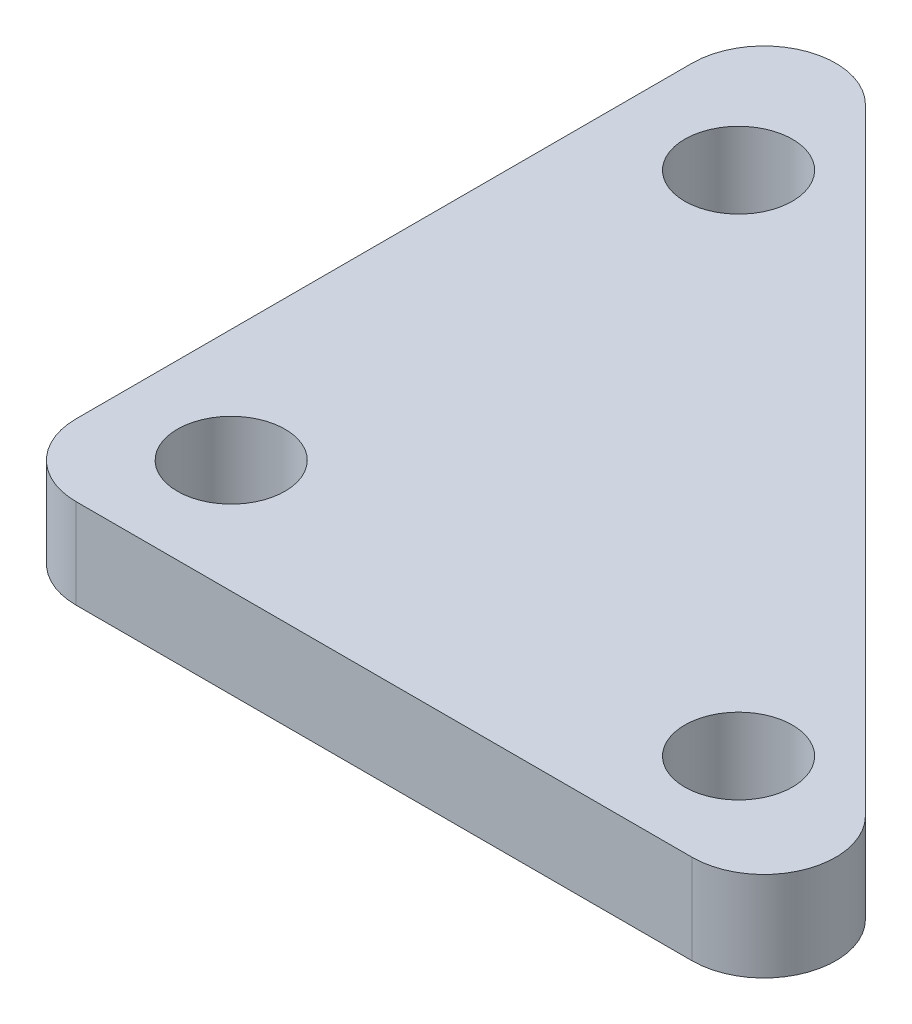
SolidWorks part; units mm, degrees
ref_plane "前视" through (0, 0, 0) normal (0, 0, 1) x (1, 0, 0)
ref_plane "上视" through (0, 0, 0) normal (0, 1, 0) x (1, 0, 0)
ref_plane "右视" through (0, 0, 0) normal (1, 0, 0) x (0, 0, -1)
sketch "Sketch1" plane through (0, 0, 0) normal (0, 1, 0) x (1, 0, 0)
  line L0 (-0.8134, -17.679) -> (23.1866, -17.679)
  line L1 (-0.8134, -17.679) -> (-0.8134, 6.321)
  line L2 (-0.8134, 6.321) -> (23.1866, -17.679)
  dimension "D1" = 24
  dimension "D2" = 24
  dimension "D3" = 33.9411
extrude "Boss-Extrude1" add sketch "Sketch1" along normal blind 2.5
fillet "Fillet1" radius 2 3 edges at (-0.8134, 1.25, 17.679) (-0.8134, 1.25, -6.321) (23.1866, 1.25, 17.679)
sketch "Sketch2" plane through (0, 2.5, 0) normal (0, 1, 0) x (1, 0, 0)
  line L2 (19.7724, -14.2648) -> (2.6008, 2.9067) construction
  circle A0 centre (2.3478, -14.5179) radius 1.5
  circle A1 centre (2.4182, -0.4462) radius 1.5
  circle A2 centre (16.5604, -14.5883) radius 1.5
  dimension "D1" = 12.5
  dimension "D3" = 2.5
  dimension "D4" = 2.5
  dimension "D5" = 20
extrude "Cut-Extrude1" cut sketch "Sketch2" against normal through all
